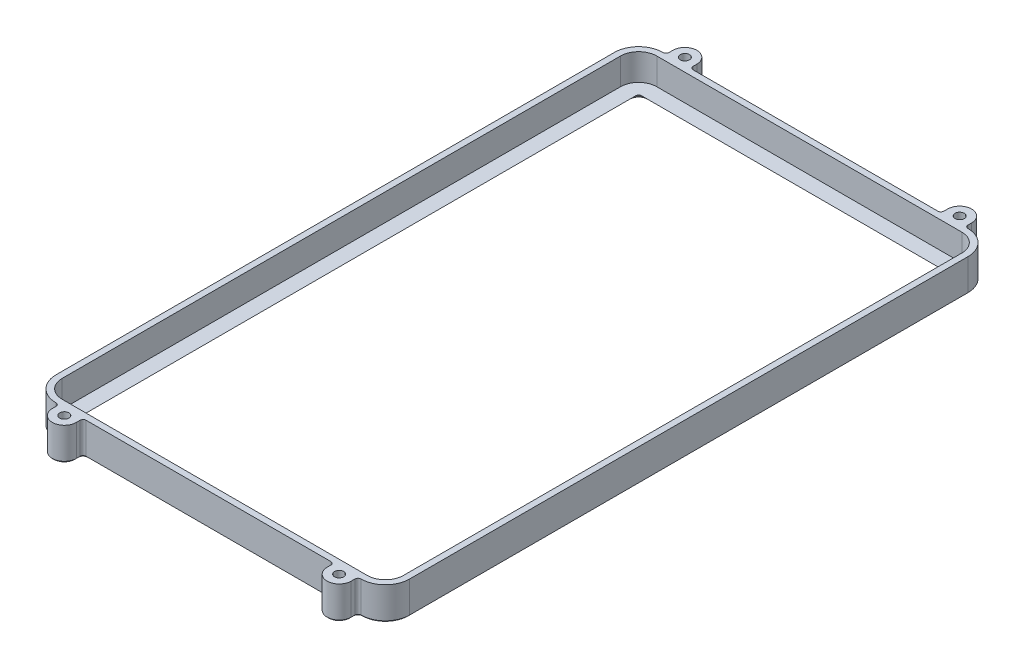
SolidWorks part; units mm, degrees
ref_plane "Front Plane" through (0, 0, 0) normal (0, 0, 1) x (1, 0, 0)
ref_plane "Top Plane" through (0, 0, 0) normal (0, 1, 0) x (1, 0, 0)
ref_plane "Right Plane" through (0, 0, 0) normal (1, 0, 0) x (0, 0, -1)
sketch "Sketch19" plane through (0, 0, 0) normal (0, 1, 0) x (-1, 0, 0)
  line L1 (-6.5603, 44.8694) -> (92.4397, 44.8694)
  line L2 (-14.4403, 36.9894) -> (-14.4403, -144.2106)
  line L3 (-6.5603, -152.0906) -> (92.4397, -152.0906)
  line L4 (100.3197, 36.9894) -> (100.3197, -144.2106)
  arc A0 (-14.4403, -144.2106) -> (-6.5603, -152.0906) centre (-6.5603, -144.2106) ccw
  arc A1 (92.4397, -152.0906) -> (100.3197, -144.2106) centre (92.4397, -144.2106) ccw
  arc A2 (100.3197, 36.9894) -> (92.4397, 44.8694) centre (92.4397, 36.9894) ccw
  arc A3 (-6.5603, 44.8694) -> (-14.4403, 36.9894) centre (-6.5603, 36.9894) ccw
  point P7 (-14.4403, -152.0906)
  point P12 (100.3197, 44.8694)
  point P15 (-14.4403, 44.8694)
  dimension "D5" = 7.88
  dimension "D3" = 114.76
  dimension "D4" = 196.96
extrude "Base" add sketch "Sketch19" along normal blind 10.64
shell "Shell" thickness 2 removed face at (-42.9397, 0, -53.6106) removed face at (-42.9397, 10.64, -53.6106)
sketch "Sketch22" plane through (0, 0, 0) normal (0, -1, 0) x (-1, 0, 0)
  line L0 (-5.5603, 154.2906) -> (-5.5603, 152.0906)
  line L1 (-6.5603, 152.0906) -> (92.4397, 152.0906) construction
  line L2 (-5.5603, 152.0906) -> (2.2397, 152.0906)
  line L3 (2.2397, 152.0906) -> (2.2397, 154.2906)
  line L4 (83.6397, 154.2906) -> (83.6397, 152.0906)
  line L5 (83.6397, 152.0906) -> (91.4397, 152.0906)
  line L6 (91.4397, 152.0906) -> (91.4397, 154.2906)
  line L7 (-5.5603, -47.0694) -> (-5.5603, -44.8694)
  line L8 (92.4397, -44.8694) -> (-6.5603, -44.8694) construction
  line L9 (-5.5603, -44.8694) -> (2.2397, -44.8694)
  line L10 (2.2397, -44.8694) -> (2.2397, -47.0694)
  line L11 (83.6397, -47.0694) -> (83.6397, -44.8694)
  line L12 (83.6397, -44.8694) -> (91.4397, -44.8694)
  line L13 (91.4397, -44.8694) -> (91.4397, -47.0694)
  line L14 (-14.4403, -36.9894) -> (-14.4403, 144.2106) construction
  line L15 (100.3197, 144.2106) -> (100.3197, -36.9894) construction
  arc A0 (-5.5603, 154.2906) -> (2.2397, 154.2906) centre (-1.6603, 154.2906) cw
  arc A1 (83.6397, 154.2906) -> (91.4397, 154.2906) centre (87.5397, 154.2906) cw
  arc A2 (-5.5603, -47.0694) -> (2.2397, -47.0694) centre (-1.6603, -47.0694) ccw
  arc A3 (83.6397, -47.0694) -> (91.4397, -47.0694) centre (87.5397, -47.0694) ccw
  dimension "D1" = 8.88
  dimension "D2" = 8.88
  dimension "D3" = 2.2
  dimension "D4" = 7.8
extrude "Clamps" add sketch "Sketch22" against normal up to surface (10.64 mm away) up to face at (-42.9397, 10.64, -53.6106)
fillet "Clamp Fillets" radius 1 8 edges at (-83.6397, 5.32, 44.8694) (5.5603, 5.32, 44.8694) (-2.2397, 5.32, 44.8694) (-91.4397, 5.32, 44.8694) (-2.2397, 5.32, -152.0906) (-91.4397, 5.32, -152.0906) (-83.6397, 5.32, -152.0906) (5.5603, 5.32, -152.0906)
sketch "Sketch25" plane through (0, 0, 0) normal (0, -1, 0) x (1, 0, 0)
  line L24 (14.4403, -144.2106) -> (14.4403, 36.9894)
  line L25 (5.5603, 45.8694) -> (5.5603, 47.0694)
  line L26 (-2.2397, 47.0694) -> (-2.2397, 45.8694)
  line L27 (-3.2397, 44.8694) -> (-82.6397, 44.8694)
  line L28 (-83.6397, 45.8694) -> (-83.6397, 47.0694)
  line L29 (-91.4397, 47.0694) -> (-91.4397, 45.8694)
  line L30 (-100.3197, 36.9894) -> (-100.3197, -144.2106)
  line L31 (-91.4397, -153.0906) -> (-91.4397, -154.2906)
  line L32 (-83.6397, -154.2906) -> (-83.6397, -153.0906)
  line L33 (-82.6397, -152.0906) -> (-3.2397, -152.0906)
  line L34 (-2.2397, -153.0906) -> (-2.2397, -154.2906)
  line L35 (5.5603, -154.2906) -> (5.5603, -153.0906)
  line L36 (14.4403, -144.2106) -> (14.4403, 36.9894)
  line L37 (5.5603, 45.8694) -> (5.5603, 47.0694)
  line L38 (-2.2397, 47.0694) -> (-2.2397, 45.8694)
  line L39 (-3.2397, 44.8694) -> (-82.6397, 44.8694)
  line L40 (-83.6397, 45.8694) -> (-83.6397, 47.0694)
  line L41 (-91.4397, 47.0694) -> (-91.4397, 45.8694)
  line L42 (-100.3197, 36.9894) -> (-100.3197, -144.2106)
  line L43 (-91.4397, -153.0906) -> (-91.4397, -154.2906)
  line L44 (-83.6397, -154.2906) -> (-83.6397, -153.0906)
  line L45 (-82.6397, -152.0906) -> (-3.2397, -152.0906)
  line L46 (-2.2397, -153.0906) -> (-2.2397, -154.2906)
  line L47 (5.5603, -154.2906) -> (5.5603, -153.0906)
  line L48 (6.5603, 37.8694) -> (-92.4397, 37.8694)
  line L49 (-93.3197, 36.9894) -> (-93.3197, -144.2106)
  line L50 (7.4403, -144.2106) -> (7.4403, 36.9894)
  line L51 (-92.4397, -145.0906) -> (6.5603, -145.0906)
  line L52 (6.5603, 37.8694) -> (-92.4397, 37.8694)
  line L53 (-93.3197, 36.9894) -> (-93.3197, -144.2106)
  line L54 (7.4403, -144.2106) -> (7.4403, 36.9894)
  line L55 (-92.4397, -145.0906) -> (6.5603, -145.0906)
  arc A4 (7.4403, 36.9894) -> (6.5603, 37.8694) centre (6.5603, 36.9894) ccw
  arc A5 (7.4403, 36.9894) -> (6.5603, 37.8694) centre (6.5603, 36.9894) ccw
  arc A6 (-92.4397, 37.8694) -> (-93.3197, 36.9894) centre (-92.4397, 36.9894) ccw
  arc A7 (-92.4397, 37.8694) -> (-93.3197, 36.9894) centre (-92.4397, 36.9894) ccw
  arc A8 (6.5603, -145.0906) -> (7.4403, -144.2106) centre (6.5603, -144.2106) ccw
  arc A9 (6.5603, -145.0906) -> (7.4403, -144.2106) centre (6.5603, -144.2106) ccw
  arc A10 (-93.3197, -144.2106) -> (-92.4397, -145.0906) centre (-92.4397, -144.2106) ccw
  arc A11 (-93.3197, -144.2106) -> (-92.4397, -145.0906) centre (-92.4397, -144.2106) ccw
  arc A24 (5.5603, 45.8694) -> (6.5603, 44.8694) centre (6.5603, 45.8694) ccw
  arc A25 (5.5603, 45.8694) -> (6.5603, 44.8694) centre (6.5603, 45.8694) ccw
  arc A26 (-92.4397, 44.8694) -> (-91.4397, 45.8694) centre (-92.4397, 45.8694) ccw
  arc A27 (-92.4397, 44.8694) -> (-91.4397, 45.8694) centre (-92.4397, 45.8694) ccw
  arc A28 (-91.4397, -153.0906) -> (-92.4397, -152.0906) centre (-92.4397, -153.0906) ccw
  arc A29 (-91.4397, -153.0906) -> (-92.4397, -152.0906) centre (-92.4397, -153.0906) ccw
  arc A30 (6.5603, -152.0906) -> (5.5603, -153.0906) centre (6.5603, -153.0906) ccw
  arc A31 (6.5603, -152.0906) -> (5.5603, -153.0906) centre (6.5603, -153.0906) ccw
  arc A32 (6.5603, -152.0906) -> (14.4403, -144.2106) centre (6.5603, -144.2106) ccw
  arc A33 (14.4403, 36.9894) -> (6.5603, 44.8694) centre (6.5603, 36.9894) ccw
  arc A35 (5.5603, 47.0694) -> (-2.2397, 47.0694) centre (1.6603, 47.0694) ccw
  arc A36 (-3.2397, 44.8694) -> (-2.2397, 45.8694) centre (-3.2397, 45.8694) ccw
  arc A37 (-83.6397, 45.8694) -> (-82.6397, 44.8694) centre (-82.6397, 45.8694) ccw
  arc A38 (-83.6397, 47.0694) -> (-91.4397, 47.0694) centre (-87.5397, 47.0694) ccw
  arc A40 (-92.4397, 44.8694) -> (-100.3197, 36.9894) centre (-92.4397, 36.9894) ccw
  arc A41 (-100.3197, -144.2106) -> (-92.4397, -152.0906) centre (-92.4397, -144.2106) ccw
  arc A43 (-91.4397, -154.2906) -> (-83.6397, -154.2906) centre (-87.5397, -154.2906) ccw
  arc A44 (-82.6397, -152.0906) -> (-83.6397, -153.0906) centre (-82.6397, -153.0906) ccw
  arc A45 (-2.2397, -153.0906) -> (-3.2397, -152.0906) centre (-3.2397, -153.0906) ccw
  arc A46 (-2.2397, -154.2906) -> (5.5603, -154.2906) centre (1.6603, -154.2906) ccw
  arc A48 (6.5603, -152.0906) -> (14.4403, -144.2106) centre (6.5603, -144.2106) ccw
  arc A49 (14.4403, 36.9894) -> (6.5603, 44.8694) centre (6.5603, 36.9894) ccw
  arc A51 (5.5603, 47.0694) -> (-2.2397, 47.0694) centre (1.6603, 47.0694) ccw
  arc A52 (-3.2397, 44.8694) -> (-2.2397, 45.8694) centre (-3.2397, 45.8694) ccw
  arc A53 (-83.6397, 45.8694) -> (-82.6397, 44.8694) centre (-82.6397, 45.8694) ccw
  arc A54 (-83.6397, 47.0694) -> (-91.4397, 47.0694) centre (-87.5397, 47.0694) ccw
  arc A56 (-92.4397, 44.8694) -> (-100.3197, 36.9894) centre (-92.4397, 36.9894) ccw
  arc A57 (-100.3197, -144.2106) -> (-92.4397, -152.0906) centre (-92.4397, -144.2106) ccw
  arc A59 (-91.4397, -154.2906) -> (-83.6397, -154.2906) centre (-87.5397, -154.2906) ccw
  arc A60 (-82.6397, -152.0906) -> (-83.6397, -153.0906) centre (-82.6397, -153.0906) ccw
  arc A61 (-2.2397, -153.0906) -> (-3.2397, -152.0906) centre (-3.2397, -153.0906) ccw
  arc A62 (-2.2397, -154.2906) -> (5.5603, -154.2906) centre (1.6603, -154.2906) ccw
  dimension "D1" = 0
  dimension "D2" = 5
extrude "Frame" add sketch "Sketch25" against normal blind 2
chamfer "Frame Chamfer" distance 2 angle 45 8 edges at (-42.9397, 0, 37.8694) (7.4403, 0, -53.6106) (-42.9397, 0, -145.0906) (-93.3197, 0, -53.6106) (7.1825, 0, 37.6116) (7.1825, 0, -144.8329) (-93.062, 0, 37.6116) (-93.062, 0, -144.8329)
sketch "Sketch23" plane through (0, 0, 0) normal (0, -1, 0) x (-1, 0, 0)
  circle A0 centre (-1.6603, 154.2906) radius 1.5
  circle A1 centre (87.5397, 154.2906) radius 1.5
  circle A2 centre (-1.6603, -47.0694) radius 1.5
  circle A3 centre (87.5397, -47.0694) radius 1.5
  arc A4 (2.2397, 154.2906) -> (-5.5603, 154.2906) centre (-1.6603, 154.2906) ccw construction
  arc A5 (91.4397, 154.2906) -> (83.6397, 154.2906) centre (87.5397, 154.2906) ccw construction
  arc A6 (-5.5603, -47.0694) -> (2.2397, -47.0694) centre (-1.6603, -47.0694) ccw construction
  arc A7 (83.6397, -47.0694) -> (91.4397, -47.0694) centre (87.5397, -47.0694) ccw construction
  dimension "D1" = 3
extrude "Clamp Holes" cut sketch "Sketch23" against normal through all
sketch "Sketch24" plane through (0, 0, 0) normal (0, -1, 0) x (1, 0, 0)
  circle A0 centre (-87.5397, 47.0694) radius 2.5
  circle A1 centre (1.6603, 47.0694) radius 2.5
  circle A2 centre (1.6603, -154.2906) radius 2.5
  circle A3 centre (-87.5397, -154.2906) radius 2.5
  arc A4 (-83.6397, 47.0694) -> (-91.4397, 47.0694) centre (-87.5397, 47.0694) ccw construction
  arc A5 (5.5603, 47.0694) -> (-2.2397, 47.0694) centre (1.6603, 47.0694) ccw construction
  arc A6 (-91.4397, -154.2906) -> (-83.6397, -154.2906) centre (-87.5397, -154.2906) ccw construction
  arc A7 (-2.2397, -154.2906) -> (5.5603, -154.2906) centre (1.6603, -154.2906) ccw construction
  dimension "D1" = 5
extrude "Clamp Countersinks" cut sketch "Sketch24" against normal blind 3
chamfer "Clamp Countersink Chamfers" distance 0.3 angle 45 4 edges at (-87.5397, 0, -156.7906) (1.6603, 0, -156.7906) (1.6603, 0, 44.5694) (-87.5397, 0, 44.5694)
chamfer "Shell Chamfer" distance 0.5 angle 45 28 edges at (-100.3197, 0, -53.6106) (-98.0117, 0, -149.7826) (-91.7326, 0, -152.3835) (-91.4397, 0, -153.6906) (-87.5397, 0, -158.1906) (-83.6397, 0, -153.6906) (-83.3468, 0, -152.3835) (-42.9397, 0, -152.0906) (-2.5326, 0, -152.3835) (-2.2397, 0, -153.6906) (1.6603, 0, -158.1906) (5.5603, 0, -153.6906) (5.8532, 0, -152.3835) (12.1323, 0, -149.7826) (14.4403, 0, -53.6106) (12.1323, 0, 42.5614) (5.8532, 0, 45.1623) (5.5603, 0, 46.4694) (1.6603, 0, 50.9694) (-2.2397, 0, 46.4694) (-2.5326, 0, 45.1623) (-42.9397, 0, 44.8694) (-83.3468, 0, 45.1623) (-83.6397, 0, 46.4694) (-87.5397, 0, 50.9694) (-91.4397, 0, 46.4694) (-91.7326, 0, 45.1623) (-98.0117, 0, 42.5614)
